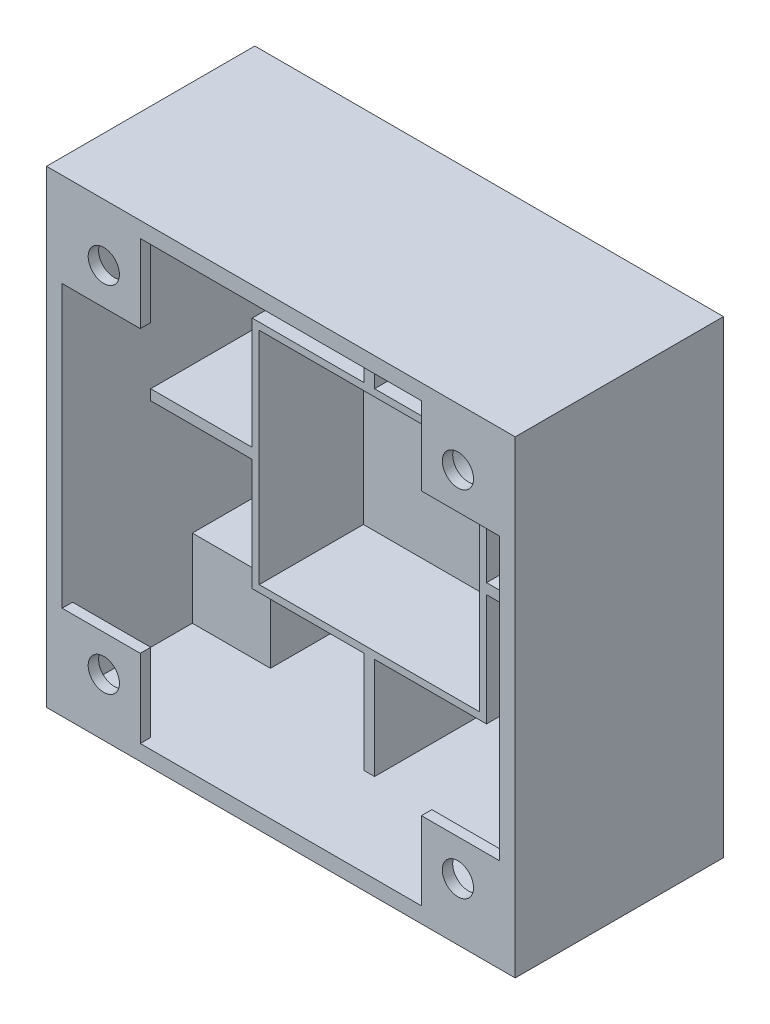
SolidWorks part; units mm, degrees
material "尼龙 101"
ref_plane "前视基准面" through (0, 0, 0) normal (0, 0, 1) x (1, 0, 0)
ref_plane "上视基准面" through (0, 0, 0) normal (0, 1, 0) x (1, 0, 0)
ref_plane "右视基准面" through (0, 0, 0) normal (1, 0, 0) x (0, 0, -1)
sketch "草图1" plane through (0, 0, 0) normal (0, 0, 1) x (1, 0, 0)
  line L1 (-45, 45) -> (45, 45)
  line L2 (-45, 45) -> (-45, -45)
  line L3 (-45, -45) -> (45, -45)
  line L4 (45, 45) -> (45, -45)
  line L5 (-45, 45) -> (45, -45) construction
  line L6 (-45, -45) -> (45, 45) construction
  point P0 (0, 0)
  dimension "D1" = 90
  dimension "D2" = 90
extrude "凸台-拉伸1" add sketch "草图1" along normal blind 40
shell "抽壳1" thickness 3 removed face at (0, 0, 40)
sketch "草图2" plane through (0, 0, 40) normal (0, 0, 1) x (1, 0, 0)
  line L0 (0, 0) -> (93.04, 0) construction
  line L1 (-42, 42) -> (-27, 42)
  line L2 (-42, 42) -> (-42, 27)
  line L3 (-42, 27) -> (-27, 27)
  line L4 (-27, 42) -> (-27, 27)
  line L5 (42, 42) -> (27, 42)
  line L6 (42, 42) -> (42, 27)
  line L7 (42, 27) -> (27, 27)
  line L8 (27, 42) -> (27, 27)
  line L9 (27, -42) -> (27, -27)
  line L10 (42, -27) -> (27, -27)
  line L11 (42, -42) -> (42, -27)
  line L12 (42, -42) -> (27, -42)
  line L13 (-27, -42) -> (-27, -27)
  line L14 (-42, -27) -> (-27, -27)
  line L15 (-42, -42) -> (-42, -27)
  line L16 (-42, -42) -> (-27, -42)
  dimension "D1" = 15
  dimension "D2" = 15
  dimension "D3" = 15
  dimension "D4" = 15
extrude "凸台-拉伸2" add sketch "草图2" against normal blind 2
sketch "草图3" plane through (0, 0, 40) normal (0, 0, 1) x (1, 0, 0)
  line L1 (0, 0) -> (0, 55.6478) construction
  line L2 (0, 0) -> (103.6974, 0) construction
  circle A0 centre (-34, 34) radius 3
  circle A1 centre (34, 34) radius 3
  circle A2 centre (34, -34) radius 3
  circle A3 centre (-34, -34) radius 3
  dimension "D3" = 6
  dimension "D4" = 6
  dimension "D5" = 6
  dimension "D6" = 6
  dimension "D1" = 68
  dimension "D2" = 68
extrude "切除-拉伸1" cut sketch "草图3" against normal up to next
sketch "草图4" plane through (0, 0, 3) normal (0, 0, 1) x (1, 0, 0)
  line L1 (-21.15, -21.15) -> (21.15, -21.15)
  line L2 (-21.15, -21.15) -> (-21.15, 21.15)
  line L3 (-21.15, 21.15) -> (21.15, 21.15)
  line L4 (21.15, -21.15) -> (21.15, 21.15)
  line L5 (-21.15, -21.15) -> (21.15, 21.15) construction
  line L6 (-21.15, 21.15) -> (21.15, -21.15) construction
  line L7 (-22.5, -22.5) -> (22.5, -22.5)
  line L8 (-22.5, -22.5) -> (-22.5, 22.5)
  line L9 (-22.5, 22.5) -> (22.5, 22.5)
  line L10 (22.5, -22.5) -> (22.5, 22.5)
  line L11 (-22.5, -22.5) -> (22.5, 22.5) construction
  line L12 (-22.5, 22.5) -> (22.5, -22.5) construction
  point P0 (0, 0)
  point P6 (0, 0)
  dimension "D1" = 42.3
  dimension "D2" = 42.3
  dimension "D3" = 45
  dimension "D4" = 45
extrude "凸台-拉伸3" add sketch "草图4" along normal blind 20
sketch "草图7" plane through (0, 0, 3) normal (0, 0, 1) x (1, 0, 0)
  line L0 (22.5, 22.5) -> (-22.5, 22.5) construction
  line L1 (-1, 42) -> (1, 42)
  line L2 (-1, 42) -> (-1, 22.5)
  line L3 (-1, 22.5) -> (1, 22.5)
  line L4 (1, 42) -> (1, 22.5)
  line L5 (-1, 42) -> (1, 22.5) construction
  line L6 (-1, 22.5) -> (1, 42) construction
  line L7 (-42, -42) -> (42, -42) construction
  line L8 (-1, -22.5) -> (1, -22.5)
  line L9 (-1, -22.5) -> (-1, -42)
  line L10 (-1, -42) -> (1, -42)
  line L11 (1, -22.5) -> (1, -42)
  line L12 (-1, -22.5) -> (1, -42) construction
  line L13 (-1, -42) -> (1, -22.5) construction
  line L14 (0, 32.25) -> (0, 0) construction
  line L15 (0, 0) -> (0, -32.25) construction
  line L16 (42, 42) -> (-42, 42) construction
  line L17 (-22.5, -22.5) -> (22.5, -22.5) construction
  point P0 (0, 32.25)
  point P7 (0, -32.25)
  dimension "D1" = 2
  dimension "D2" = 2
extrude "凸台-拉伸5" add sketch "草图7" along normal up to surface (20 mm away) up to face at (0, 0, 23)
ref_axis "基准轴1" through (0, 0, -2) along (0, 0, 1)
pattern_circular "阵列(圆周)1" count 2 over 90 about axis through (0, 0, -2) along (0, 0, 1) of "凸台-拉伸5"
sketch "草图9" plane through (0, 0, 3) normal (0, 0, 1) x (1, 0, 0)
  line L0 (42, 42) -> (1, 42) construction
  line L1 (1, 22.5) -> (1, 42) construction
  line L2 (22.5, 22.5) -> (1, 22.5) construction
  line L3 (22.5, 1) -> (22.5, 22.5) construction
  line L4 (42, 1) -> (22.5, 1) construction
  line L5 (42, 1) -> (42, 42) construction
  line L6 (42, 42) -> (1, 42)
  line L7 (1, 22.5) -> (1, 42)
  line L8 (22.5, 22.5) -> (1, 22.5)
  line L9 (22.5, 1) -> (22.5, 22.5)
  line L10 (42, 1) -> (22.5, 1)
  line L11 (42, 1) -> (42, 42)
  line L12 (0, 0) -> (61.621, 0) construction
  line L13 (-22.5, -22.5) -> (-22.5, -1) construction
  line L14 (-22.5, -1) -> (-42, -1) construction
  line L15 (-42, -1) -> (-42, -42) construction
  line L16 (-42, -42) -> (-1, -42) construction
  line L17 (-1, -42) -> (-1, -22.5) construction
  line L18 (-1, -22.5) -> (-22.5, -22.5) construction
  line L19 (-42, 42) -> (-42, 1)
  line L20 (-42, 1) -> (-22.5, 1)
  line L21 (-22.5, 1) -> (-22.5, 22.5)
  line L22 (-22.5, 22.5) -> (-1, 22.5)
  line L23 (-1, 22.5) -> (-1, 42)
  line L24 (-1, 42) -> (-42, 42)
  line L25 (-42, 42) -> (-42, 1)
  line L26 (-42, 1) -> (-22.5, 1)
  line L27 (-22.5, 1) -> (-22.5, 22.5)
  line L28 (-22.5, 22.5) -> (-1, 22.5)
  line L29 (-1, 22.5) -> (-1, 42)
  line L30 (-1, 42) -> (-42, 42)
  line L31 (42, -42) -> (42, -1) construction
  line L32 (42, -1) -> (22.5, -1) construction
  line L33 (22.5, -1) -> (22.5, -22.5) construction
  line L34 (22.5, -22.5) -> (1, -22.5) construction
  line L35 (1, -22.5) -> (1, -42) construction
  line L36 (1, -42) -> (42, -42) construction
  line L37 (-22.5, -22.5) -> (-22.5, -1)
  line L38 (-22.5, -1) -> (-42, -1)
  line L39 (-42, -1) -> (-42, -42)
  line L40 (-42, -42) -> (-1, -42)
  line L41 (-1, -42) -> (-1, -22.5)
  line L42 (-1, -22.5) -> (-22.5, -22.5)
  line L43 (42, -42) -> (42, -1)
  line L44 (42, -1) -> (22.5, -1)
  line L45 (22.5, -1) -> (22.5, -22.5)
  line L46 (22.5, -22.5) -> (1, -22.5)
  line L47 (1, -22.5) -> (1, -42)
  line L48 (1, -42) -> (42, -42)
  dimension "D1" = 0
extrude "切除-拉伸2" cut sketch "草图9" against normal through all
sketch "草图10" plane through (0, 0, 0) normal (0, 0, -1) x (-1, 0, 0)
  circle A0 centre (0, 0) radius 5
  dimension "D1" = 10
extrude "切除-拉伸3" cut sketch "草图10" against normal through all
sketch "草图11" plane through (0, 0, 0) normal (0, 0, -1) x (-1, 0, 0)
  line L0 (-42, -42) -> (-27, -42) construction
  line L1 (-27, -42) -> (-27, -27) construction
  line L2 (-27, -27) -> (-42, -27) construction
  line L3 (-42, -27) -> (-42, -42) construction
  line L4 (27, -42) -> (42, -42) construction
  line L5 (42, -42) -> (42, -27) construction
  line L6 (42, -27) -> (27, -27) construction
  line L7 (27, -27) -> (27, -42) construction
  line L8 (42, 27) -> (42, 42) construction
  line L9 (42, 42) -> (27, 42) construction
  line L10 (27, 42) -> (27, 27) construction
  line L11 (27, 27) -> (42, 27) construction
  line L12 (-42, 42) -> (-42, 27) construction
  line L13 (-42, 27) -> (-27, 27) construction
  line L14 (-27, 27) -> (-27, 42) construction
  line L15 (-27, 42) -> (-42, 42) construction
  line L16 (-42, -42) -> (-27, -42)
  line L17 (-27, -42) -> (-27, -27)
  line L18 (-27, -27) -> (-42, -27)
  line L19 (-42, -27) -> (-42, -42)
  line L20 (27, -42) -> (42, -42)
  line L21 (42, -42) -> (42, -27)
  line L22 (42, -27) -> (27, -27)
  line L23 (27, -27) -> (27, -42)
  line L24 (42, 27) -> (42, 42)
  line L25 (42, 42) -> (27, 42)
  line L26 (27, 42) -> (27, 27)
  line L27 (27, 27) -> (42, 27)
  line L28 (-42, 42) -> (-42, 27)
  line L29 (-42, 27) -> (-27, 27)
  line L30 (-27, 27) -> (-27, 42)
  line L31 (-27, 42) -> (-42, 42)
extrude "凸台-拉伸6" add sketch "草图11" against normal blind 15
sketch "草图12" plane through (0, 0, 0) normal (0, 0, -1) x (-1, 0, 0)
  circle A0 centre (34, 34) radius 3 construction
  circle A1 centre (34, -34) radius 3 construction
  circle A2 centre (-34, -34) radius 3 construction
  circle A3 centre (-34, 34) radius 3 construction
  circle A4 centre (34, 34) radius 3
  circle A5 centre (34, -34) radius 3
  circle A6 centre (-34, -34) radius 3
  circle A7 centre (-34, 34) radius 3
extrude "切除-拉伸4" cut sketch "草图12" against normal blind 10
